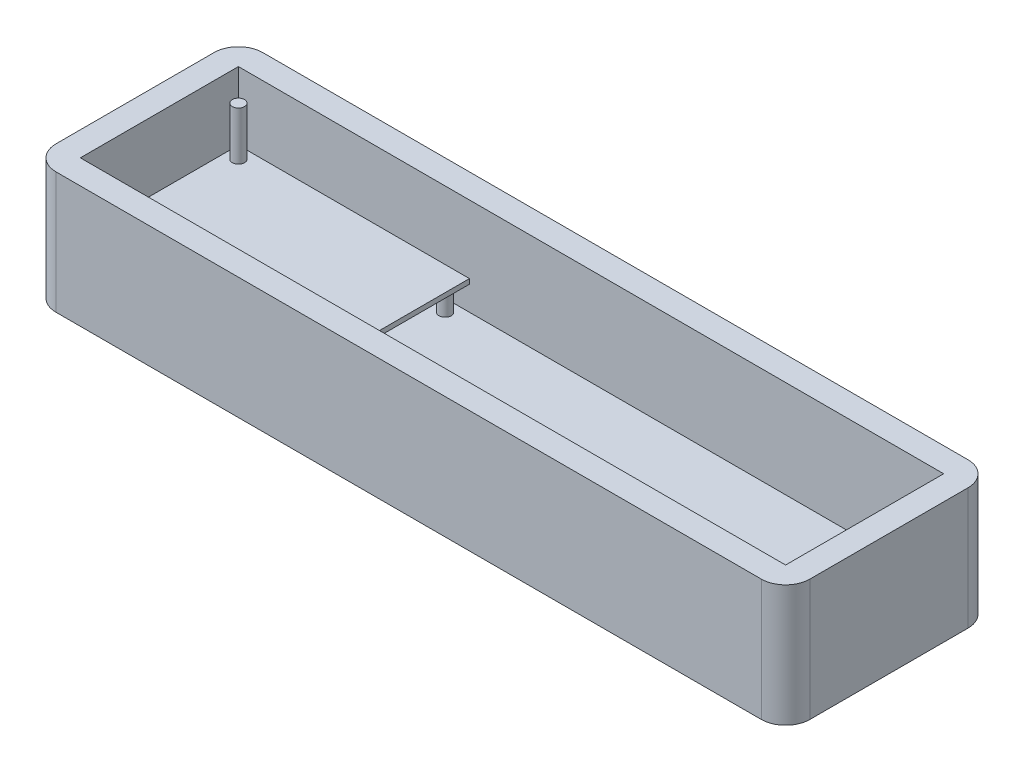
SolidWorks part; units mm, degrees
ref_plane "Ebene vorne" through (0, 0, 0) normal (0, 0, 1) x (1, 0, 0)
ref_plane "Ebene oben" through (0, 0, 0) normal (0, 1, 0) x (1, 0, 0)
ref_plane "Ebene rechts" through (0, 0, 0) normal (1, 0, 0) x (0, 0, -1)
sketch "Skizze2" plane through (0, 0, 0) normal (0, 0, 1) x (1, 0, 0)
  line L1 (0, 0) -> (310, 0)
  line L2 (0, 0) -> (0, 50)
  line L3 (0, 50) -> (310, 50)
  line L4 (310, 0) -> (310, 50)
  dimension "D1" = 310
  dimension "D2" = 50
extrude "Aufsatz-Linear austragen1" add sketch "Skizze2" along normal blind 85
sketch "Skizze4" plane through (0, 50, 0) normal (0, 1, 0) x (1, 0, 0)
  line L0 (310, 0) -> (0, 0) construction
  line L1 (10, -10) -> (300, -10)
  line L2 (10, -10) -> (10, -75)
  line L3 (10, -75) -> (300, -75)
  line L4 (300, -10) -> (300, -75)
  line L5 (310, -85) -> (0, -85) construction
  line L6 (0, -85) -> (0, 0) construction
  line L7 (310, -85) -> (310, 0) construction
  dimension "D1" = 10
  dimension "D2" = 10
  dimension "D3" = 10
  dimension "D4" = 10
extrude "Schnitt-Linear austragen1" cut sketch "Skizze4" against normal blind 40
sketch "Skizze5" plane through (0, 10, 0) normal (0, 1, 0) x (1, 0, 0)
  line L0 (10, -10) -> (10, -75) construction
  line L1 (10, -75) -> (300, -75) construction
  line L2 (300, -10) -> (10, -10) construction
  circle A0 centre (15, -15) radius 2.5
  circle A1 centre (15, -70) radius 2.5
  circle A2 centre (100, -70) radius 2.5
  circle A3 centre (100, -15) radius 2.5
  dimension "D1" = 5
  dimension "D2" = 5
  dimension "D3" = 5
  dimension "D4" = 5
  dimension "D5" = 5
  dimension "D6" = 5
  dimension "D7" = 5
  dimension "D8" = 5
  dimension "D9" = 5
  dimension "D10" = 5
  dimension "D11" = 85
  dimension "D12" = 85
  dimension "D13" = 55
extrude "Aufsatz-Linear austragen3" add sketch "Skizze5" along normal blind 10
sketch "Skizze6" plane through (0, 20, 0) normal (0, 1, 0) x (1, 0, 0)
  line L1 (300, -10) -> (10, -10) construction
  line L2 (10, -10) -> (105, -10)
  line L3 (10, -10) -> (10, -75)
  line L4 (10, -75) -> (105, -75)
  line L5 (105, -10) -> (105, -75)
  line L6 (10, -10) -> (10, -75) construction
  line L7 (10, -75) -> (300, -75) construction
  circle A1 centre (100, -15) radius 2.5 construction
  dimension "D1" = 0
  dimension "D2" = 0
  dimension "D3" = 0
  dimension "D4" = 5
extrude "Aufsatz-Linear austragen4" add sketch "Skizze6" along normal blind 2
sketch "Skizze7" plane through (0, 22, 0) normal (0, 1, 0) x (1, 0, 0)
  line L0 (10, -10) -> (10, -75) construction
  line L1 (10, -75) -> (105, -75) construction
  line L2 (105, -10) -> (10, -10) construction
  circle A0 centre (15, -15) radius 2.5
  circle A1 centre (15, -70) radius 2.5
  dimension "D1" = 5
  dimension "D2" = 5
  dimension "D3" = 5
  dimension "D4" = 5
  dimension "D5" = 5
  dimension "D6" = 5
extrude "Aufsatz-Linear austragen5" add sketch "Skizze7" along normal blind 20
sketch "Skizze8" plane through (0, 10, 0) normal (0, 1, 0) x (1, 0, 0)
  line L0 (300, -75) -> (300, -10) construction
  line L1 (10, -75) -> (300, -75) construction
  line L2 (300, -10) -> (10, -10) construction
  circle A0 centre (295, -15) radius 2.5
  circle A1 centre (295, -70) radius 2.5
  dimension "D1" = 5
  dimension "D2" = 5
  dimension "D3" = 5
  dimension "D4" = 5
  dimension "D5" = 5
  dimension "D6" = 5
extrude "Aufsatz-Linear austragen6" add sketch "Skizze8" along normal blind 30
fillet "Verrundung1" radius 10 1 edges at (310, 25, 0)
fillet "Verrundung2" radius 10 1 edges at (310, 25, 85)
fillet "Verrundung3" radius 10 1 edges at (0, 25, 85)
fillet "Verrundung4" radius 10 1 edges at (0, 25, 0)
